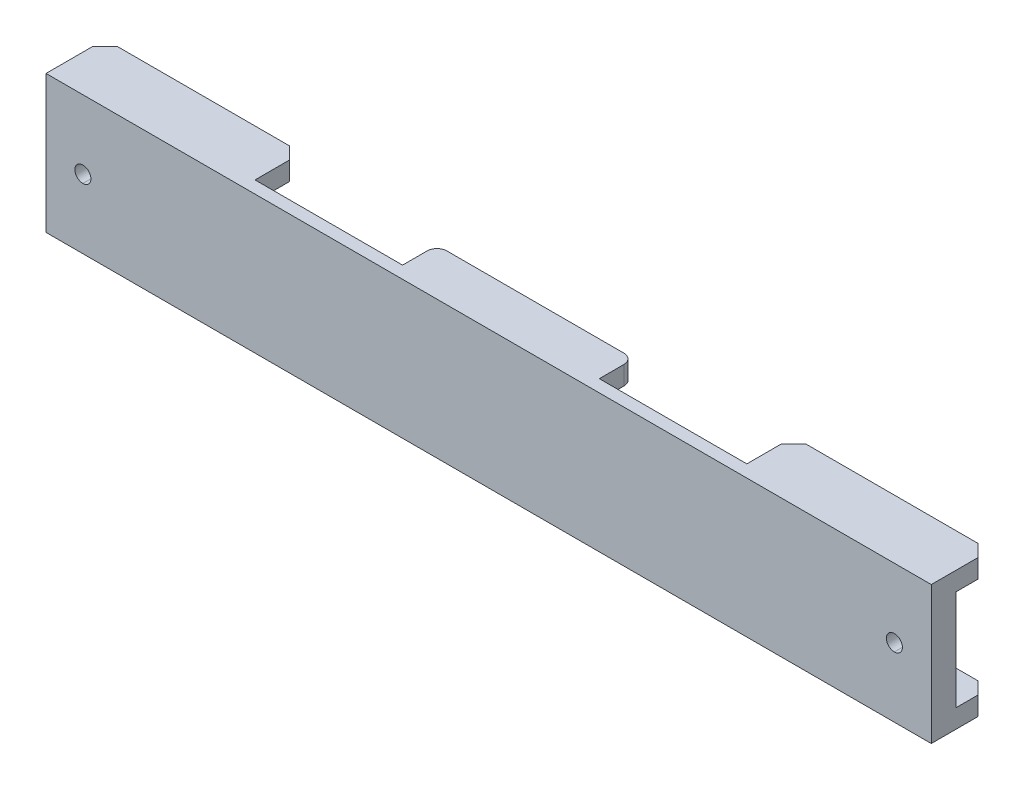
SolidWorks part; units mm, degrees
ref_plane "Front Plane" through (0, 0, 0) normal (0, 0, 1) x (1, 0, 0)
ref_plane "Top Plane" through (0, 0, 0) normal (0, 1, 0) x (1, 0, 0)
ref_plane "Right Plane" through (0, 0, 0) normal (1, 0, 0) x (0, 0, -1)
ref_plane "Plane1" through (0, 10, 0) normal (0, 1, 0) x (1, 0, 0)
sketch "Sketch1" plane through (0, 0, 0) normal (0, 0, 1) x (1, 0, 0)
  line L0 (-150, 20) -> (0, 20) construction
  line L1 (15, -4) -> (-165, -4)
  line L2 (15, -4) -> (15, 24)
  line L3 (15, 24) -> (-165, 24)
  line L4 (-165, -4) -> (-165, 24)
  line L5 (-150, 0) -> (-150, 20) construction
  line L6 (0, 0) -> (-150, 0) construction
  point P6 (-75, 20)
  point P7 (-75, 24)
  point P10 (-150, 10)
  point P11 (-165, 10)
  dimension "D1" = 4
  dimension "D2" = 15
extrude "Boss-Extrude1" add sketch "Sketch1" along normal blind 5 contours L4 L3 L2 L1
sketch "Sketch2" plane through (0, -4, 0) normal (0, -1, 0) x (-1, 0, 0)
  line L1 (-15, 0) -> (25, 0)
  line L2 (-15, 0) -> (-15, 7)
  line L3 (-15, 7) -> (25, 7)
  line L4 (25, 0) -> (25, 7)
  line L5 (-15, 0) -> (165, 0) construction
  line L6 (55, 0) -> (95, 0)
  line L7 (55, 0) -> (55, 4.5)
  line L8 (55, 4.5) -> (95, 4.5)
  line L9 (95, 0) -> (95, 4.5)
  line L10 (0, 7) -> (150, 7) construction
  line L11 (0, 7) -> (0, 0) construction
  line L12 (75, -5) -> (75, 17.0857) construction
  line L13 (-15, -5) -> (165, -5) construction
  line L14 (165, 7) -> (125, 7)
  line L15 (125, 0) -> (125, 7)
  line L16 (165, 0) -> (125, 0)
  line L17 (165, 0) -> (165, 7)
  line L18 (-15, -5) -> (-15, 0) construction
  point P24 (75, 0)
  dimension "D1" = 25
  dimension "D2" = 2.5
  dimension "D3" = 40
extrude "Boss-Extrude2" add sketch "Sketch2" against normal offset from surface (3.8 mm away) 0.2
chamfer "Chamfer1" distance 2.5 angle 45 4 edges at (-165, -2.1, -7) (-125, -2.1, -7) (15, -2.1, -7) (-25, -2.1, -7)
fillet "Fillet1" radius 2 2 edges at (-55, -2.1, -4.5) (-95, -2.1, -4.5)
mirror "Mirror1" about plane through (0, 10, 0) normal (0, 1, 0) of bodies 102
sketch "Sketch3" plane through (0, 0, 0) normal (0, 0, -1) x (-1, 0, 0)
  line L0 (-15, 20.2) -> (25, 20.2) construction
  line L1 (-2.5, 20.2) -> (-0.5, 20.2)
  line L2 (-2.5, 20.2) -> (-2.5, 15.2)
  line L3 (-2.5, 15.2) -> (-0.5, 15.2)
  line L4 (-0.5, 20.2) -> (-0.5, 15.2)
  line L5 (0, 20) -> (0, 0) construction
  line L6 (-15, -0.2) -> (25, -0.2) construction
  line L7 (-2.5, -0.2) -> (-0.5, -0.2)
  line L8 (-2.5, -0.2) -> (-2.5, 4.8)
  line L9 (-2.5, 4.8) -> (-0.5, 4.8)
  line L10 (-0.5, -0.2) -> (-0.5, 4.8)
  line L11 (75, 24) -> (75, -4) construction
  line L12 (93, 24) -> (57, 24) construction
  line L13 (93, -4) -> (57, -4) construction
  line L14 (152.5, 20.2) -> (150.5, 20.2)
  line L15 (150.5, 20.2) -> (150.5, 15.2)
  line L16 (152.5, 20.2) -> (152.5, 15.2)
  line L17 (152.5, 15.2) -> (150.5, 15.2)
  line L18 (152.5, -0.2) -> (150.5, -0.2)
  line L19 (152.5, -0.2) -> (152.5, 4.8)
  line L20 (152.5, 4.8) -> (150.5, 4.8)
  line L21 (150.5, -0.2) -> (150.5, 4.8)
  dimension "D1" = 0.5
  dimension "D2" = 5
  dimension "D3" = 2
extrude "Boss-Extrude3" add sketch "Sketch3" along normal blind 2
sketch "Sketch4" plane through (0, 0, 0) normal (0, 0, -1) x (-1, 0, 0)
  line L0 (0, 10) -> (-15, 10) construction
  line L1 (0, 20) -> (0, 0) construction
  line L2 (-15, -0.2) -> (-15, 20.2) construction
  line L3 (-7.51, 10) -> (-7.49, 10) construction
  line L4 (-7.51, 11.62) -> (-7.49, 11.62)
  line L5 (-7.51, 8.38) -> (-7.49, 8.38)
  line L6 (75, 24) -> (75, -4) construction
  line L7 (93, 24) -> (57, 24) construction
  line L8 (93, -4) -> (57, -4) construction
  line L9 (157.51, 10) -> (157.49, 10) construction
  line L10 (157.51, 11.62) -> (157.49, 11.62)
  line L11 (157.51, 8.38) -> (157.49, 8.38)
  arc A0 (-7.51, 11.62) -> (-7.51, 8.38) centre (-7.51, 10) ccw
  arc A1 (-7.49, 8.38) -> (-7.49, 11.62) centre (-7.49, 10) ccw
  arc A2 (157.51, 11.62) -> (157.51, 8.38) centre (157.51, 10) cw
  arc A3 (157.49, 8.38) -> (157.49, 11.62) centre (157.49, 10) cw
  point P8 (-7.5, 10)
  point P21 (157.5, 10)
  dimension "D1" = 1.62
  dimension "D2" = 0.02
extrude "Cut-Extrude1" cut sketch "Sketch4" against normal through all
sketch "Sketch6" plane through (0, 0, 0) normal (0, 0, -1) x (-1, 0, 0)
  line L0 (-7.51, 11.62) -> (-7.49, 11.62) construction
  line L1 (75, 24) -> (75, -4) construction
  line L2 (75, 24) -> (75, -4) construction
  circle A0 centre (-7.5, 10) radius 1.62
  circle A1 centre (157.5, 10) radius 1.62
extrude "Cut-Extrude4" [suppressed] cut sketch "Sketch6" against normal through all
sketch "Sketch5" plane through (0, -4, 0) normal (0, -1, 0) x (1, 0, 0)
  line L0 (-40, 0) -> (-40, 5) construction
  line L1 (-25, 0) -> (-55, 0) construction
  line L2 (15, 5) -> (-165, 5) construction
  line L4 (-25, 0) -> (-55, 0)
  line L5 (-25, 0) -> (-25, 2.5)
  line L6 (-25, 2.5) -> (-55, 2.5)
  line L7 (-55, 0) -> (-55, 2.5)
  line L8 (-55, -2.5) -> (-55, 0) construction
  line L9 (-75, -4.5) -> (-75, 5) construction
  line L10 (-93, -4.5) -> (-57, -4.5) construction
  line L11 (-125, 2.5) -> (-95, 2.5)
  line L12 (-95, 0) -> (-95, 2.5)
  line L13 (-125, 0) -> (-95, 0)
  line L14 (-125, 0) -> (-125, 2.5)
  point P13 (-40, 2.5)
  point P14 (-40, 2.5)
extrude "Cut-Extrude2" cut sketch "Sketch5" against normal up to surface (3.8 mm away) up to face at (-2.4, -0.2, -2.7)
extrude "Cut-Extrude3" cut sketch "Sketch5<2>" along normal up to surface (-24.2 mm away) from surface up to face at (-2.4, 20.2, -2.7) starting at face at (-75, 24, -2.8238)
sketch "Sketch5<2>" plane through (0, -4, 0) normal (0, -1, 0) x (1, 0, 0) same geometry as "Sketch5"
sketch "Sketch7" plane through (0, 0, 0) normal (0, 0, -1) x (-1, 0, 0)
  line L0 (-2.5, 20.2) -> (-2.5, 15.2) construction
  line L1 (-11.5, 0.8) -> (-3.5, 0.8)
  line L2 (-11.5, 0.8) -> (-11.5, 19.2)
  line L3 (-11.5, 19.2) -> (-3.5, 19.2)
  line L4 (-3.5, 0.8) -> (-3.5, 19.2)
  line L5 (-7.5, 19.2) -> (-7.5, 0.8) construction
  line L6 (-11.5, 10) -> (-3.5, 10) construction
  line L7 (-15, 20.2) -> (-2.5, 20.2) construction
  line L8 (-7.49, 11.62) -> (-7.51, 11.62) construction
  arc A0 (-7.51, 11.62) -> (-7.51, 8.38) centre (-7.51, 10) ccw construction
  circle A1 centre (-7.5, 10) radius 1.7
  point P0 (-7.5, 10)
  point P13 (-9.13, 10)
  point P16 (-7.5, 11.62)
  dimension "D3" = 3.4
  dimension "D1" = 1
  dimension "D2" = 1
extrude "Boss-Extrude4" add sketch "Sketch7" along normal blind 3.5 separate body
fillet "Fillet2" radius 2 4 edges at (3.5, 0.8, -1.75) (11.5, 0.8, -1.75) (11.5, 19.2, -1.75) (3.5, 19.2, -1.75)
